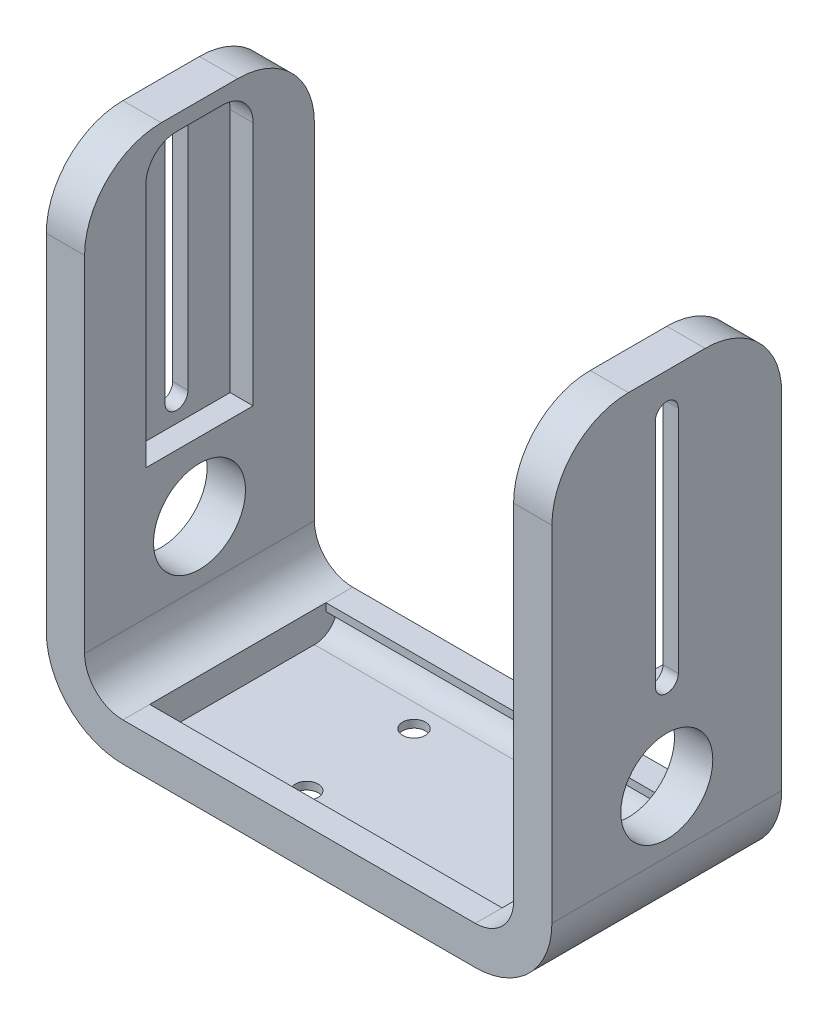
SolidWorks part; units mm, degrees
material "Titanium Ti-8Mn, Annealed"
ref_plane "Front Plane" through (0, 0, 0) normal (0, 0, 1) x (1, 0, 0)
ref_plane "Top Plane" through (0, 0, 0) normal (0, 1, 0) x (1, 0, 0)
ref_plane "Right Plane" through (0, 0, 0) normal (1, 0, 0) x (0, 0, -1)
sketch "Sketch1" plane through (0, 0, 0) normal (0, 0, 1) x (1, 0, 0)
  line L0 (5, 0) -> (60, 0)
  line L1 (0, 5) -> (0, 60)
  line L2 (5, -5) -> (60, -5)
  line L3 (-5, 5) -> (-5, 60)
  line L4 (60, 0) -> (60, -5)
  line L5 (0, 60) -> (-5, 60)
  arc A0 (5, 0) -> (0, 5) centre (5, 5) cw
  arc A1 (5, -5) -> (-5, 5) centre (5, 5) cw
  point P6 (0, 0)
  dimension "D3" = 5
  dimension "D1" = 60
  dimension "D2" = 60
  dimension "D4" = 5
extrude "Boss-Extrude1" add sketch "Sketch1" along normal mid plane 30
sketch "Sketch2" plane through (60, 0, 0) normal (1, 0, 0) x (0, 0, -1)
  line L0 (-11.5, 0) -> (-11.5, -1)
  line L1 (-15, 0) -> (15, 0) construction
  line L2 (-11.5, -1) -> (-13, -1)
  line L3 (-13, -1) -> (-13, -4)
  line L4 (-13, -4) -> (13, -4)
  line L5 (13, -4) -> (13, -1)
  line L6 (13, -1) -> (11.5, -1)
  line L7 (11.5, -1) -> (11.5, 0)
  line L8 (11.5, 0) -> (-11.5, 0)
  line L9 (-15, -5) -> (15, -5) construction
  line L10 (-15, -5) -> (-15, 0) construction
  line L11 (15, -5) -> (15, 0) construction
  dimension "D1" = 1
  dimension "D2" = 1
  dimension "D3" = 2
  dimension "D4" = 2
  dimension "D5" = 1.5
sketch "Sketch3" plane through (0, 0, 0) normal (0, 1, 0) x (1, 0, 0)
  line L0 (60, 0) -> (5, 0)
  line L1 (60, -13) -> (60, 13) construction
  line L2 (5, -15) -> (5, 15) construction
sweep "Cut-Sweep1" cut profiles "Sketch2" path "Sketch3"
sketch "Sketch4" plane through (0, 0, 0) normal (1, 0, 0) x (0, 0, -1)
  line L0 (0, 55) -> (0, 25) construction
  line L1 (1.5, 55) -> (1.5, 25)
  line L2 (-1.5, 55) -> (-1.5, 25)
  line L6 (-15, 60) -> (15, 60) construction
  arc A0 (1.5, 55) -> (-1.5, 55) centre (0, 55) ccw
  arc A1 (-1.5, 25) -> (1.5, 25) centre (0, 25) ccw
  point P3 (0, 40)
  dimension "D1" = 1.5
  dimension "D2" = 30
  dimension "D3" = 20
extrude "Cut-Extrude1" cut sketch "Sketch4" against normal blind 30
sketch "Sketch5" plane through (0, 0, 0) normal (1, 0, 0) x (0, 0, -1)
  line L0 (15, 5) -> (15, 60) construction
  line L1 (-7, 58) -> (7, 58)
  line L2 (-7, 58) -> (-7, 22)
  line L3 (-7, 22) -> (7, 22)
  line L4 (7, 58) -> (7, 22)
  line L6 (-15, 60) -> (15, 60) construction
  line L7 (0, 53.8929) -> (0, 17.8929) construction
  dimension "D1" = 8
  dimension "D2" = 2
  dimension "D3" = 36
extrude "Cut-Extrude2" cut sketch "Sketch5" against normal blind 3
sketch "Sketch7" plane through (0, -4, 0) normal (0, 1, 0) x (1, 0, 0)
  line L0 (60, 13) -> (60, -13) construction
  line L1 (60, 0) -> (5, 0) construction
  line L2 (5, 11.5) -> (5, -11.5) construction
  circle A0 centre (35, 7) radius 1.5
  circle A1 centre (35, -7) radius 1.5
  dimension "D3" = 3
  dimension "D1" = 14
  dimension "D2" = 25
extrude "Cut-Extrude3" cut sketch "Sketch7" against normal through all
ref_plane "Plane1" through (28, 0, 0) normal (1, 0, 0) x (0, 0, -1)
mirror "Mirror1" about plane through (28, 0, 0) normal (1, 0, 0) of "Cut-Extrude3", "Cut-Extrude2", "Cut-Extrude1", "Boss-Extrude1", "Cut-Sweep1"
sketch "Sketch8" plane through (0, 0, 15) normal (0, 0, 1) x (1, 0, 0)
  line L0 (61, 5) -> (65.7557, 5)
  line L1 (51, -5) -> (51, -9.7557)
  line L2 (5, -5) -> (5, -11.5748)
  line L3 (-5, 5) -> (-11.5748, 5)
  line L4 (0, 5) -> (-5, 5)
  line L5 (5, 0) -> (5, -5)
  circle A0 centre (51, 5) radius 10
  circle A1 centre (51, 5) radius 14.7557
  circle A2 centre (5, 5) radius 10
  circle A3 centre (5, 5) radius 16.5748
  circle A4 centre (5, 5) radius 5
  arc M3 (-5, 5) -> (-3.6603, 0) centre (5, 5) ccw
  line M4 (-3.6603, 0) -> (-4, 0)
  line M5 (-4, 0) -> (-4, -5)
  line M6 (-4, -5) -> (60, -5)
  line M7 (60, -5) -> (60, 0)
  line M8 (60, 0) -> (59.6603, 0)
  arc M9 (59.6603, 0) -> (61, 5) centre (51, 5) ccw
  arc M15 (5, 0) -> (0, 5) centre (5, 5) cw
  dimension "D1" = 29.5114
  dimension "D2" = 20
  dimension "D3" = 33.1497
  dimension "D4" = 10
extrude "Cut-Extrude5" cut sketch "Sketch8" against normal blind 70 contours L1 A1 L0 M9 M8 M7 M6 | A0 M6 M7 M8 | A2 M4 M5 M6 region at (63.3778, 4.7913, 15) region at (57.8809, -3.4666, 15) region at (-1.8809, -3.4666, 15)
extrude "Boss-Extrude2" add sketch "Sketch8<3>" against normal up to surface (30 mm away) contours A2 L5 L4 M3 M15 region at (0.0485, 0.0485, 15) up to face at (28, 20.3156, -15)
sketch "Sketch8<3>" plane through (0, 0, 15) normal (0, 0, 1) x (1, 0, 0) same geometry as "Sketch8"
fillet "Fillet1" radius 10 4 edges at (-2.5, 60, -15) (-2.5, 60, 15) (58.5, 60, 15) (58.5, 60, -15)
fillet "Fillet2" radius 4 4 edges at (57.5, 58, 7) (57.5, 58, -7) (-1.5, 58, -7) (-1.5, 58, 7)
fillet "Fillet3" radius 3 2 edges at (28, -4, 13) (28, -4, -13)
sketch "Sketch9" plane through (-5, 0, 0) normal (-1, 0, 0) x (0, 0, 1)
  line L0 (0, 5) -> (0, 13)
  line L1 (15, 5) -> (-15, 5) construction
  circle A0 centre (0, 13) radius 6
  dimension "D2" = 12
  dimension "D1" = 8
extrude "Cut-Extrude6" cut sketch "Sketch9" against normal blind 83 contours A0 region at (-5, 8.8774, 4.1226)
